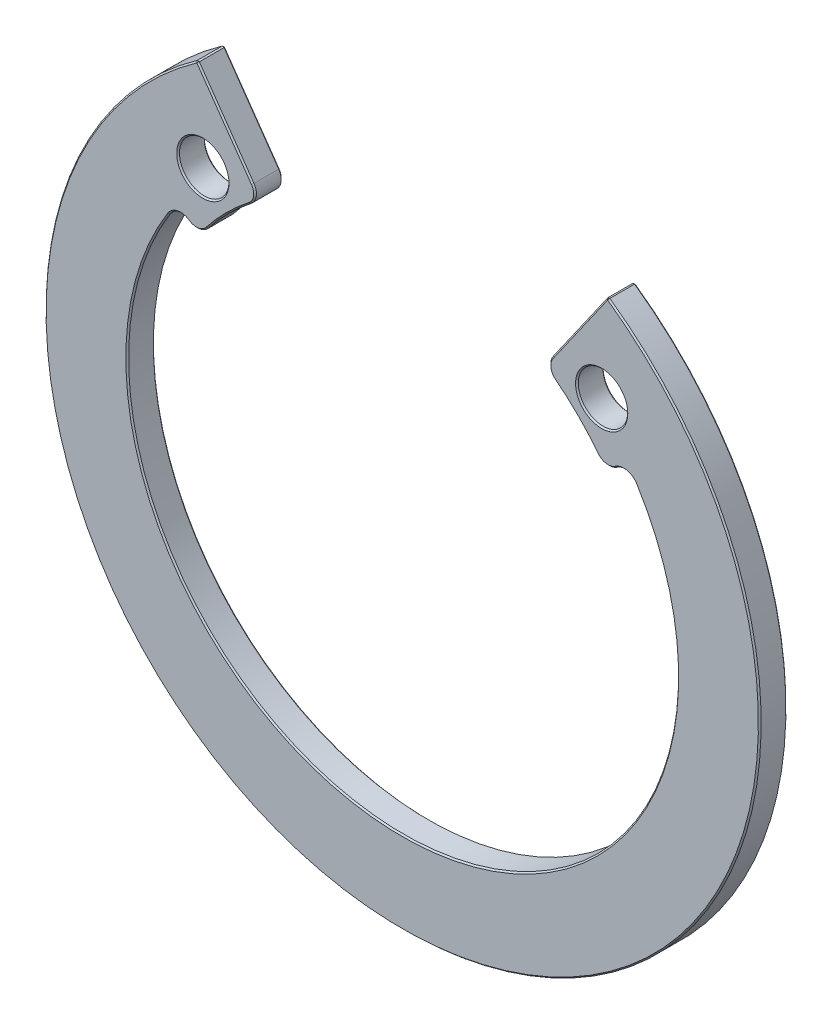
SolidWorks part; units mm, degrees
ref_plane "Piano frontale" through (0, 0, 0) normal (0, 0, 1) x (1, 0, 0)
ref_plane "Piano superiore" through (0, 0, 0) normal (0, 1, 0) x (1, 0, 0)
ref_plane "Piano destro" through (0, 0, 0) normal (1, 0, 0) x (0, 0, -1)
sketch "Schizzo1" plane through (0, 0, 0) normal (0, 0, 1) x (1, 0, 0)
  line L0 (0, 0) -> (0, 16.0197) construction
  line L1 (5.1622, 7.3724) -> (7.4565, 10.649)
  line L2 (-5.1622, 7.3724) -> (-7.4565, 10.649)
  line L3 (7.3724, 5.1622) -> (8.1915, 5.7358)
  line L4 (-7.3724, 5.1622) -> (-8.1915, 5.7358)
  arc A0 (-7.4565, 10.649) -> (7.4565, 10.649) centre (0, 0) ccw
  arc A1 (-8.1915, 5.7358) -> (8.1915, 5.7358) centre (0, 0) ccw
  arc A2 (7.3724, 5.1622) -> (5.1622, 7.3724) centre (0, 0) ccw
  arc A3 (-5.1622, 7.3724) -> (-7.3724, 5.1622) centre (0, 0) ccw
  circle A4 centre (-7.2504, 7.3732) radius 0.9
  circle A5 centre (7.2504, 7.3732) radius 0.9
  dimension "D1" = 20
  dimension "D2" = 26
  dimension "D4" = 18
  dimension "D6" = 1.8
  dimension "D3" = 35
  dimension "D5" = 20
  dimension "D7" = 7.2504
extrude "Estrusione-Estrusione1" add sketch "Schizzo1" along normal blind 1
fillet "Raccordo2" radius 0.5 6 edges at (5.1622, 7.3724, 0.5) (7.3724, 5.1622, 0.5) (8.1915, 5.7358, 0.5) (-5.1622, 7.3724, 0.5) (-7.3724, 5.1622, 0.5) (-8.1915, 5.7358, 0.5)
chamfer "Smusso2" distance 0.05 angle 45 30 edges at (6.3504, 7.3732, 0) (-6.3504, 7.3732, 0) (6.3504, 7.3732, 1) (7.4565, 10.649, 0.5) (7.4105, 5.3565, 0) (8.1577, 5.5218, 0) (0, -10, 0) (-8.1577, 5.5218, 0) (-7.4105, 5.3565, 0) (-6.364, 6.364, 0) (-5.3565, 7.4105, 0) (-6.449, 9.2101, 0) (6.364, 6.364, 0) (5.3565, 7.4105, 0) (6.449, 9.2101, 0) (0, -13, 0) (-7.4565, 10.649, 0.5) (0, -13, 1) (-6.449, 9.2101, 1) (-5.3565, 7.4105, 1) (-6.364, 6.364, 1) (-7.4105, 5.3565, 1) (-8.1577, 5.5218, 1) (0, -10, 1) (8.1577, 5.5218, 1) (7.4105, 5.3565, 1) (6.364, 6.364, 1) (5.3565, 7.4105, 1) (6.449, 9.2101, 1) (-6.3504, 7.3732, 1)
